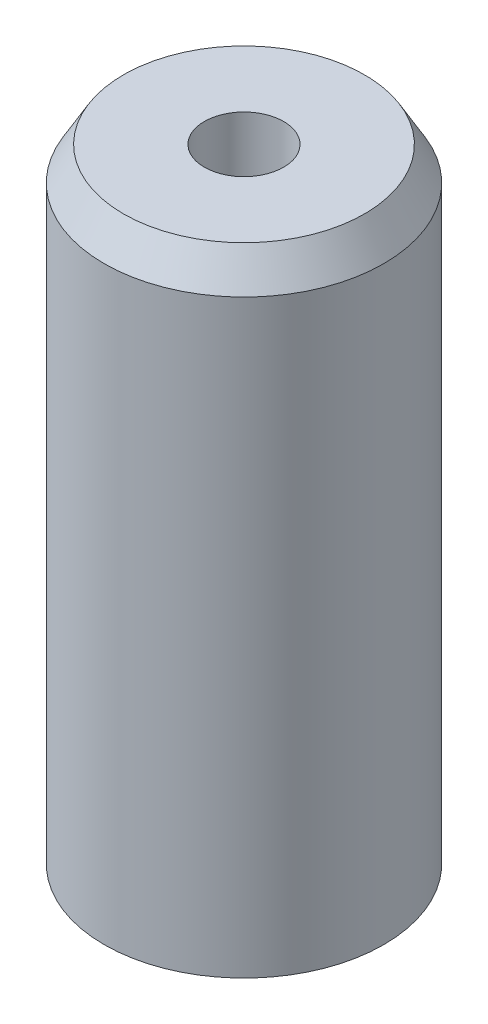
SolidWorks part; units mm, degrees
ref_plane "Front Plane" through (0, 0, 0) normal (0, 0, 1) x (1, 0, 0)
ref_plane "Top Plane" through (0, 0, 0) normal (0, 1, 0) x (1, 0, 0)
ref_plane "Right Plane" through (0, 0, 0) normal (1, 0, 0) x (0, 0, -1)
sketch "Sketch1" plane through (0, 0, 0) normal (0, 1, 0) x (1, 0, 0)
  circle A0 centre (0, 0) radius 15
  dimension "SHAFT_OD" = 30
extrude "Boss-Extrude1" add sketch "Sketch1" along normal blind 68.9309
sketch "Sketch2" plane through (0, 0, 0) normal (0, 1, 0) x (1, 0, 0)
  circle A0 centre (0, 0) radius 4.2537
  dimension "BORE_D" = 8.5074
extrude "Cut-Extrude1" cut sketch "Sketch2" along normal through all
chamfer "Chamfer1" distance 3.5862 angle 30 2 edges at (0, 68.9309, 15) (0, 0, 15) first distance on face at (0, 68.9309, 15) first distance on face at (0, 0, 4.2537)
